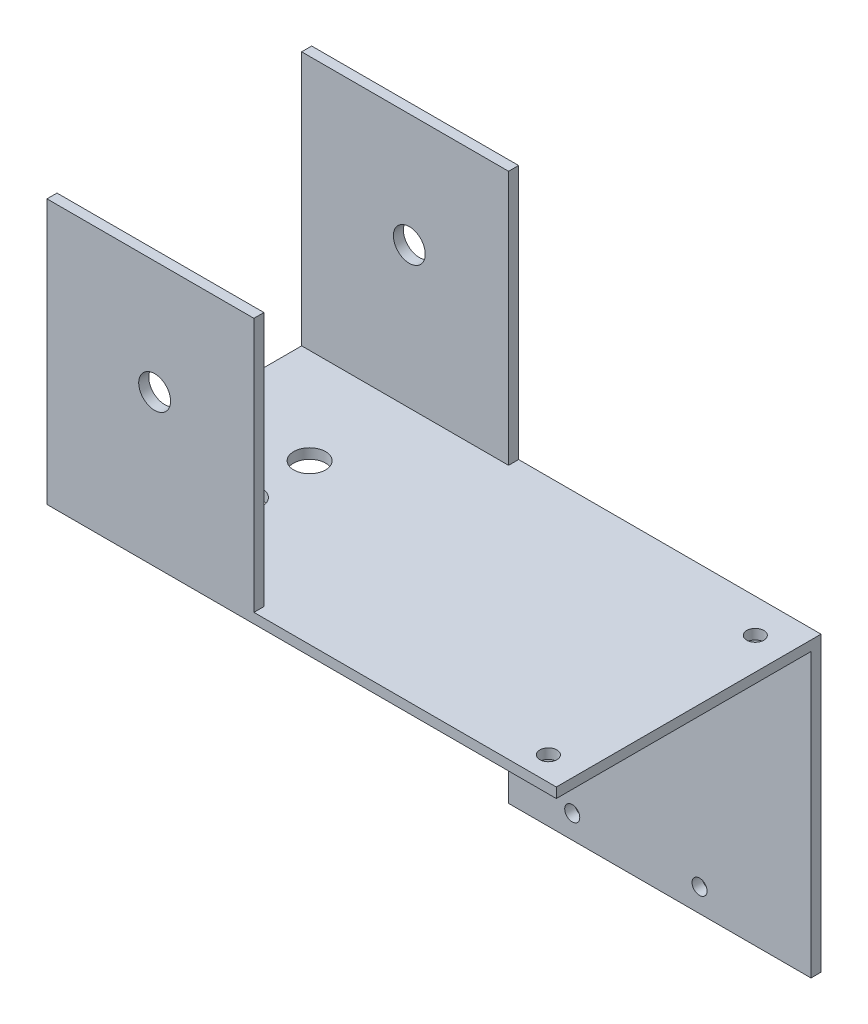
SolidWorks part; units mm, degrees
material "Galvanized Steel"
ref_plane "Front Plane" through (0, 0, 0) normal (0, 0, 1) x (1, 0, 0)
ref_plane "Top Plane" through (0, 0, 0) normal (0, 1, 0) x (1, 0, 0)
ref_plane "Right Plane" through (0, 0, 0) normal (1, 0, 0) x (0, 0, -1)
sketch "Sketch1" plane through (0, 0, 0) normal (0, 0, 1) x (1, 0, 0)
  line L0 (38.1, 51.75) -> (12.7, 51.75) construction
  line L1 (0, 58.4) -> (60.325, 58.4)
  line L2 (0, 58.4) -> (0, 0)
  line L3 (0, 0) -> (60.325, 0)
  line L4 (60.325, 58.4) -> (60.325, 0)
  line L6 (12.7, 51.75) -> (12.7, 4.65) construction
  line L8 (12.7, 4.65) -> (38.1, 4.65) construction
  line L9 (38.1, 51.75) -> (38.1, 4.65) construction
  circle A4 centre (12.7, 51.75) radius 1.5
  circle A5 centre (38.1, 51.75) radius 1.5
  circle A6 centre (12.7, 4.65) radius 1.5
  circle A7 centre (38.1, 4.65) radius 1.5
  dimension "D3" = 3
  dimension "D1" = 58.4
  dimension "D4" = 47.1
  dimension "D6" = 4.65
  dimension "D7" = 25.4
  dimension "D9" = 12.7
  dimension "D11" = 60.325
extrude "Boss-Extrude1" add sketch "Sketch1" against normal blind 2
sketch "Sketch2" plane through (0, 0, -2) normal (0, 0, -1) x (-1, 0, 0)
  line L0 (0, 56.4) -> (41.275, 56.4)
  line L1 (0, 58.4) -> (0, 0) construction
  line L2 (0, 56.4) -> (-60.325, 56.4)
  line L3 (-60.325, 56.4) -> (-60.325, 58.4)
  line L5 (-60.325, 58.4) -> (0, 58.4)
  line L6 (41.275, 56.4) -> (41.275, 58.4)
  line L7 (41.275, 58.4) -> (0, 58.4)
  dimension "D1" = 60.325
  dimension "D2" = 41.275
  dimension "D3" = 2
extrude "Boss-Extrude2" add sketch "Sketch2" against normal blind 52.8
sketch "Sketch3" plane through (0, 58.4, 0) normal (0, 1, 0) x (1, 0, 0)
  line L0 (53.975, -4.7625) -> (53.975, -46.0375) construction
  line L1 (-20.6375, -19.05) -> (-20.6375, -31.75) construction
  line L2 (60.325, -50.8) -> (60.325, 2) construction
  line L3 (-41.275, -50.8) -> (60.325, -50.8) construction
  line L4 (-41.275, -50.8) -> (60.325, -50.8) construction
  line L5 (-41.275, -50.8) -> (-41.275, 2) construction
  circle A0 centre (53.975, -4.7625) radius 1.7
  circle A1 centre (53.975, -46.0375) radius 1.7
  circle A2 centre (-20.6375, -31.75) radius 3.175
  circle A3 centre (-20.6375, -19.05) radius 3.175
  dimension "D1" = 3.4
  dimension "D2" = 41.275
  dimension "D5" = 6.35
  dimension "D6" = 6.35
  dimension "D3" = 4.7625
  dimension "D4" = 6.35
  dimension "D7" = 12.7
  dimension "D8" = 19.05
  dimension "D9" = 20.6375
extrude "Cut-Extrude1" cut sketch "Sketch3" against normal through all
sketch "Sketch4" plane through (0, 58.4, 0) normal (0, 1, 0) x (1, 0, 0)
  line L0 (60.325, 2) -> (-41.275, 2) construction
  line L1 (0, 2) -> (-41.275, 2)
  line L2 (0, 2) -> (0, 0)
  line L3 (0, 0) -> (-41.275, 0)
  line L4 (-41.275, 2) -> (-41.275, 0)
  line L5 (-41.275, -50.8) -> (-41.275, 2) construction
  line L7 (-41.275, -50.8) -> (0, -50.8)
  line L8 (-41.275, -50.8) -> (-41.275, -48.8)
  line L9 (-41.275, -48.8) -> (0, -48.8)
  line L10 (0, -50.8) -> (0, -48.8)
  dimension "D1" = 2
  dimension "D2" = 2
extrude "Boss-Extrude3" add sketch "Sketch4" along normal blind 50.8
sketch "Sketch5" plane through (0, 0, 50.8) normal (0, 0, 1) x (1, 0, 0)
  line L0 (0, 58.4) -> (60.325, 58.4) construction
  line L1 (-41.275, 56.4) -> (-41.275, 109.2) construction
  circle A0 centre (-19.8, 86.568) radius 3.175
  dimension "D2" = 6.35
  dimension "D1" = 28.168
  dimension "D3" = 21.475
extrude "Cut-Extrude2" cut sketch "Sketch5" against normal through all
